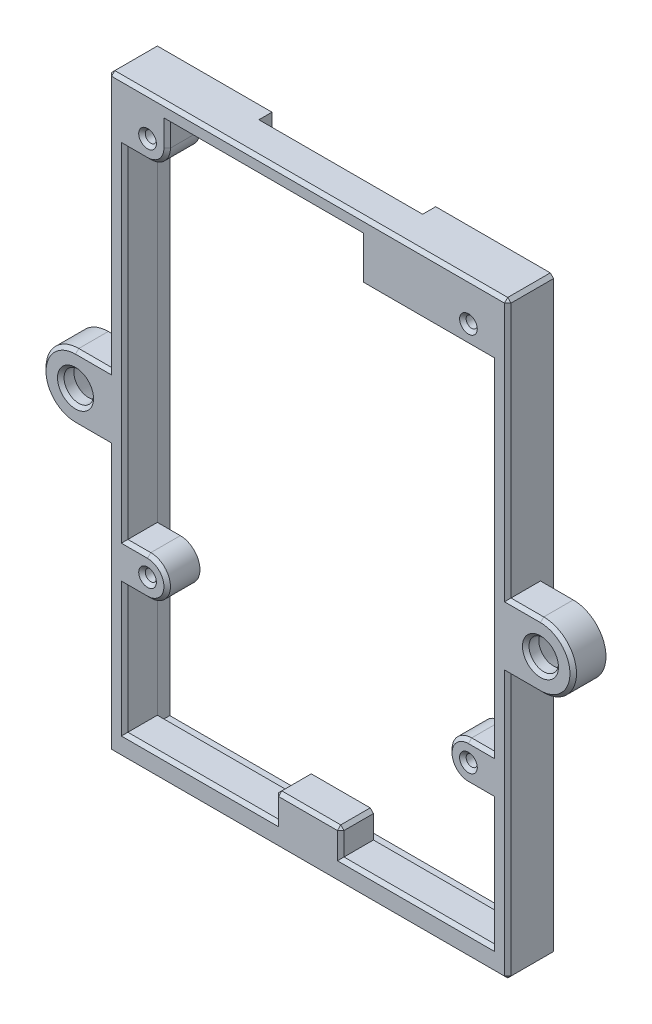
SolidWorks part; units mm, degrees
ref_plane "Front Plane" through (0, 0, 0) normal (0, 0, 1) x (1, 0, 0)
ref_plane "Top Plane" through (0, 0, 0) normal (0, 1, 0) x (1, 0, 0)
ref_plane "Right Plane" through (0, 0, 0) normal (1, 0, 0) x (0, 0, -1)
sketch "Sketch1" plane through (0, 0, 0) normal (0, 0, 1) x (1, 0, 0)
  line L0 (-23, -43) -> (-23, 35.9019) construction
  line L1 (23, -43) -> (28, -43) construction
  line L2 (-28, -42) -> (-28, 42) construction
  line L3 (-28, 42) -> (28, 42) construction
  line L4 (28, -42) -> (28, -22.5) construction
  line L5 (-22.8417, 36) -> (23, 36) construction
  line L6 (23, 35.5) -> (23, -43) construction
  line L7 (-23, -43) -> (-28, -43) construction
  line L8 (-30.5, -43) -> (-30.5, 44.5)
  line L9 (-30.5, 44.5) -> (30.5, 44.5)
  line L10 (30.5, 44.5) -> (30.5, -43)
  line L11 (28, -43) -> (23, -43) construction
  line L12 (-21.5, 38.5) -> (-21.5, 42)
  line L13 (-24.5, 35.5) -> (-28, 35.5)
  line L14 (-23, 35.9019) -> (-23, 36) construction
  line L15 (-23, 36) -> (-22.8417, 36) construction
  line L16 (8, 42) -> (-21.5, 42)
  line L17 (8, 42) -> (8, 35.5)
  line L18 (8, 35.5) -> (24.5, 35.5)
  line L19 (24.5, 35.5) -> (28, 35.5)
  line L20 (23, 36) -> (23, 35.9019) construction
  line L21 (23, 35.9019) -> (23, 35.5) construction
  line L22 (-24.5, -16.5) -> (-28, -16.5)
  line L23 (-28, -16.5) -> (-28, 35.5)
  line L24 (-24.5, -22.5) -> (-28, -22.5)
  line L25 (-28, -22.5) -> (-28, -42)
  line L26 (-28, -43) -> (-30.5, -43) construction
  line L27 (-30.5, -43) -> (-30.5, -45.5)
  line L28 (-30.5, -45.5) -> (30.5, -45.5)
  line L29 (30.5, -45.5) -> (30.5, -43)
  line L30 (-23, -43) -> (23, -43) construction
  line L31 (30.5, -43) -> (28, -43) construction
  line L32 (24.5, -16.5) -> (28, -16.5)
  line L33 (28, -16.5) -> (28, 35.5)
  line L34 (24.5, -22.5) -> (28, -22.5)
  line L35 (28, -22.5) -> (28, -42)
  line L36 (28, -22.5) -> (28, -16.5) construction
  line L37 (28, -16.5) -> (28, 42) construction
  line L38 (-28, -42) -> (-5, -42)
  line L39 (-28, -42) -> (-28, -43) construction
  line L40 (-28, -43) -> (-28, -42) construction
  line L41 (-28, -43) -> (-23, -43) construction
  line L42 (-23, -43) -> (23, -43) construction
  line L43 (28, -43) -> (28, -42) construction
  line L44 (28, -42) -> (28, -43) construction
  line L45 (0, -42) -> (0, -38) construction
  line L46 (0, -38) -> (-5, -38)
  line L47 (-5, -38) -> (-5, -42)
  line L48 (0, -38) -> (5, -38)
  line L49 (5, -38) -> (5, -42)
  line L50 (-5, -42) -> (0, -42) construction
  line L51 (5, -42) -> (28, -42)
  line L52 (0, -42) -> (5, -42) construction
  circle A0 centre (-24.5, 38.5) radius 0.85
  circle A1 centre (24.5, 38.5) radius 0.85
  arc A4 (-24.5, 35.5) -> (-21.5, 38.5) centre (-24.5, 38.5) ccw
  arc A5 (-21.5, 38.5) -> (-24.5, 35.5) centre (-24.5, 38.5) ccw construction
  arc A6 (23, 35.9019) -> (24.5, 35.5) centre (24.5, 38.5) ccw construction
  arc A7 (24.5, 35.5) -> (22.8417, 36) centre (24.5, 38.5) ccw construction
  arc A8 (22.8417, 36) -> (23, 35.9019) centre (24.5, 38.5) ccw construction
  circle A9 centre (24.5, -19.5) radius 0.85
  arc A10 (24.5, -16.5) -> (24.5, -22.5) centre (24.5, -19.5) ccw
  circle A11 centre (-24.5, -19.5) radius 0.85
  arc A12 (-24.5, -22.5) -> (-24.5, -16.5) centre (-24.5, -19.5) ccw
  arc A13 (-24.5, -16.5) -> (-24.5, -22.5) centre (-24.5, -19.5) ccw construction
  arc A14 (24.5, -22.5) -> (24.5, -16.5) centre (24.5, -19.5) ccw construction
  point P4 (0, 42)
  point P5 (-28, 0)
  dimension "D6" = 1.7
  dimension "D14" = 6
  dimension "D15" = 6
  dimension "D1" = 56
  dimension "D2" = 85
  dimension "D3" = 5
  dimension "D4" = 5
  dimension "D5" = 6
  dimension "D7" = 3.5
  dimension "D8" = 3.5
  dimension "D9" = 3.5
  dimension "D10" = 3.5
  dimension "D11" = 7.5
  dimension "D12" = 7.5
  dimension "D13" = 8.5
  dimension "D16" = 58
  dimension "D17" = 20
  dimension "D18" = 58
  dimension "D19" = 2.5
  dimension "D20" = 1
  dimension "D21" = 5
  dimension "D22" = 5
  dimension "D23" = 5
extrude "Boss-Extrude1" add sketch "Sketch1" along normal blind 5
sketch "Sketch2" plane through (0, 0, 0) normal (0, 0, 1) x (1, 0, 0)
  line L2 (30.5, 44.5) -> (30.5, -45.5)
  line L3 (30.5, -45.5) -> (28.1, -45.5)
  line L4 (28.1, 42.1) -> (28.1, -43.1)
  line L6 (-30.5, 44.5) -> (-30.5, -45.5)
  line L7 (-30.5, -45.5) -> (-28.1, -45.5)
  line L8 (-28.1, 42.1) -> (-28.1, -43.1)
  line L11 (28.1, 42.1) -> (-28.1, 42.1)
  line L12 (28, -42) -> (28, -22.5) construction
  line L14 (-30.5, -45.5) -> (30.5, -45.5) construction
  line L15 (-28, -42) -> (-28, 42) construction
  line L16 (-28, 42) -> (28, 42) construction
  line L17 (-28.1, -43.1) -> (28.1, -43.1)
  line L18 (-5, -38) -> (5, -38) construction
  line L19 (-28.1, -43.1) -> (-28.1, -45.5) construction
  line L20 (28.1, -43.1) -> (28.1, -45.5) construction
  line L21 (-28.1, -45.5) -> (28.1, -45.5)
  line L22 (-30.5, 44.5) -> (30.5, 44.5)
  dimension "D1" = 0.1
  dimension "D2" = 0.1
  dimension "D3" = 0.1
  dimension "D4" = 5.1
extrude "Boss-Extrude2" add sketch "Sketch2" against normal blind 2 contours L11 L4 L3 L2 L6 L7 L8 region at (29.4128, -0.5, 0)
sketch "Sketch3" plane through (0, 0, 0) normal (0, 0, 1) x (1, 0, 0)
  line L0 (30.5, 44.5) -> (30.5, -43) construction
  line L1 (35.5, 5) -> (30.5, 5)
  line L3 (35.5, -5) -> (30.5, -5)
  line L4 (30.5, 5) -> (30.5, -5)
  line L5 (-30.5, -43) -> (-30.5, 44.5) construction
  line L6 (-35.5, 5) -> (-30.5, 5)
  line L8 (-35.5, -5) -> (-30.5, -5)
  line L9 (-30.5, 5) -> (-30.5, -5)
  arc A0 (35.5, -5) -> (35.5, 5) centre (35.5, 0) ccw
  arc A1 (-35.5, 5) -> (-35.5, -5) centre (-35.5, 0) ccw
  circle A2 centre (35.5, 0) radius 2.25
  circle A3 centre (-35.5, 0) radius 2.25
  dimension "D1" = 10
  dimension "D2" = 10
  dimension "D3" = 4.5
  dimension "D4" = 4.5
extrude "Boss-Extrude3" add sketch "Sketch3" along normal up to surface (5 mm away) up to face at (25.35, 38.5, 5)
sketch "Sketch4" plane through (0, 0, 0) normal (0, 0, -1) x (-1, 0, 0)
  circle A0 centre (-35.5, 0) radius 3.5
  circle A1 centre (35.5, 0) radius 3.5
  dimension "D1" = 7
  dimension "D2" = 7
extrude "Cut-Extrude1" cut sketch "Sketch4" against normal blind 3
sketch "Sketch5" plane through (0, 0, 0) normal (0, 0, -1) x (-1, 0, 0)
  line L0 (30.5, 44.5) -> (-30.5, 44.5) construction
  line L5 (12.5, 44.5) -> (-12.5, 44.5)
  line L6 (12.5, 44.5) -> (12.5, 42.1)
  line L11 (12.5, 42.1) -> (-12.5, 42.1)
  line L12 (-12.5, 44.5) -> (-12.5, 42.1)
  line L13 (-28.1, 42.1) -> (28.1, 42.1) construction
  point P0 (-24.5, 38.5)
  point P9 (0, 44.5)
  point P10 (0, 44.5)
  dimension "D1" = 25
extrude "Cut-Extrude2" cut sketch "Sketch5" along normal through all
chamfer "Chamfer3" distance 0.5 angle 45 50 edges at (-37.75, 0, 5) (33.25, 0, 5) (25.35, 38.5, 5) (-23.65, 38.5, 5) (-30.5, -25.25, 5) (-33, -5, 5) (-40.5, 0, 5) (-33, 5, 5) (-30.5, 24.75, 5) (0, 44.5, 5) (30.5, 24.75, 5) (33, 5, 5) (40.5, 0, 5) (33, -5, 5) (30.5, -25.25, 5) (-23.65, 38.5, 0) (25.35, 38.5, 0) (-23.65, -19.5, 5) (25.35, -19.5, 5) (-26.25, 35.5, 5) (-28, 9.5, 5) (-26.25, -16.5, 5) (-21.5, -19.5, 5) (-26.25, -22.5, 5) (-28, -32.25, 5) (-16.5, -42, 5) (-5, -40, 5) (0, -38, 5) (5, -40, 5) (16.5, -42, 5) (28, -32.25, 5) (26.25, -22.5, 5) (21.5, -19.5, 5) (26.25, -16.5, 5) (28, 9.5, 5) (18, 35.5, 5) (8, 38.75, 5) (-6.75, 42, 5) (-21.5, 40.25, 5) (-22.3787, 36.3787, 5) (0, -45.5, 5) (-23.65, -19.5, 0) (25.35, -19.5, 0) (30.5, -45.5, 1.5) (-30.5, -45.5, 1.5) (-30.5, 44.5, 1.5) (30.5, 44.5, 1.5) (-5, -38, 2.5) (5, -38, 2.5) (8, 35.5, 2.5)
chamfer "Chamfer1" distance 2.5 distance2 1.25 2 edges at (-39, 0, 3) (32, 0, 3) first distance on face at (-39, 0, 3) first distance on face at (32, 0, 3)
